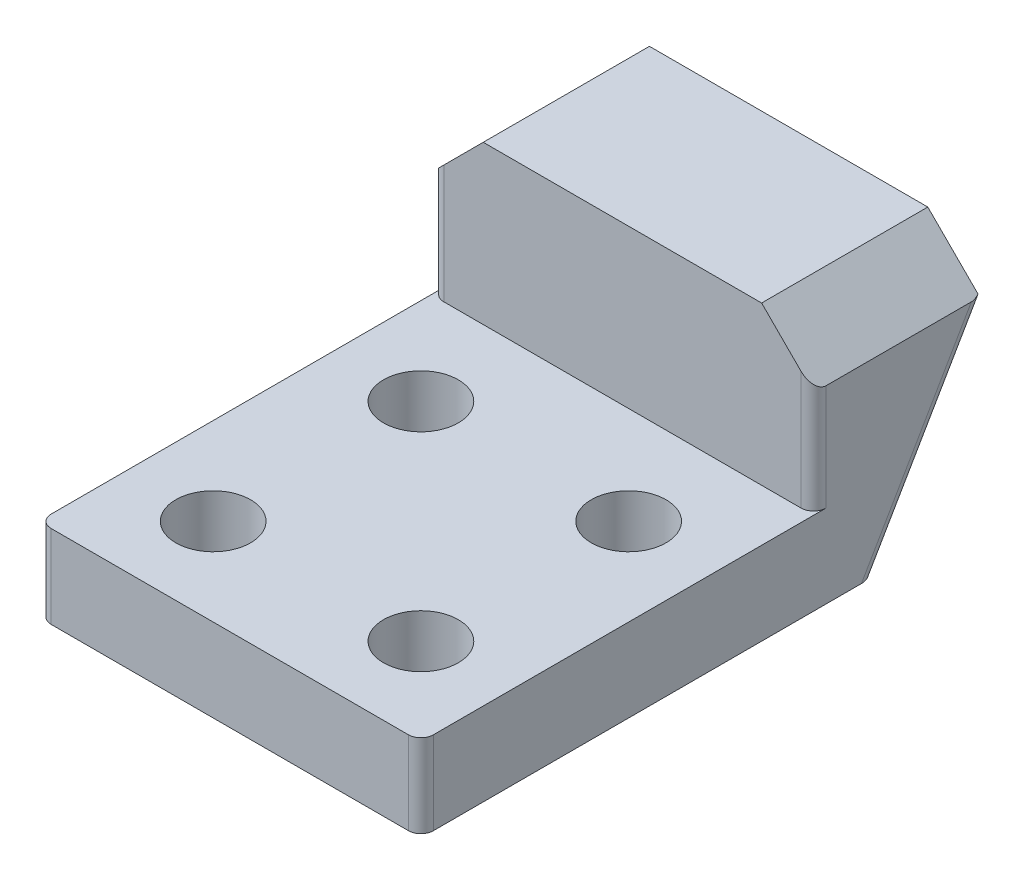
SolidWorks part; units mm, degrees
ref_plane "Front Plane" through (0, 0, 0) normal (0, 0, 1) x (1, 0, 0)
ref_plane "Top Plane" through (0, 0, 0) normal (0, 1, 0) x (1, 0, 0)
ref_plane "Right Plane" through (0, 0, 0) normal (1, 0, 0) x (0, 0, -1)
sketch "Sketch1" plane through (0, 0, 0) normal (0, 1, 0) x (1, 0, 0)
  line L1 (0, 0) -> (18.4, 0)
  line L2 (0, 0) -> (0, 21.9)
  line L3 (0, 21.9) -> (18.4, 21.9)
  line L4 (18.4, 0) -> (18.4, 21.9)
  dimension "D1" = 18.4
  dimension "D2" = 21.9
extrude "Boss-Extrude1" add sketch "Sketch1" along normal blind 4
sketch "Sketch2" plane through (0, 4, 0) normal (0, 1, 0) x (1, 0, 0)
  line L0 (9.2, 0) -> (9.2, 21.9) construction
  line L1 (0, 0) -> (18.4, 0) construction
  line L2 (18.4, 21.9) -> (0, 21.9) construction
  line L4 (4.2, 4.2) -> (4.2, 14.2) construction
  point P0 (4.2, 4.2)
  point P15 (4.2, 14.2)
  point P18 (3.1567, 13.0582)
  point P21 (14.2, 14.2)
  point P22 (14.2, 4.2)
  point P23 (0, 0)
  dimension "D1" = 5
  dimension "D2" = 10
  dimension "D3" = 4.2
hole_wizard "M3 Clearance Hole1" positions "Sketch2" profile "Sketch3" hole size "M3" standard "ANSI Metric" end condition through all
sketch "Sketch3" plane through (4.2, 4, -4.2) normal (1, 0, 0) x (0, 0, 1)
  line L0 (0, 0) -> (0, 4)
  line L1 (0, 4) -> (1.8, 4)
  line L2 (1.8, 4) -> (1.8, 0)
  line L5 (1.8, 0) -> (0, 0)
  line L11 (0, -6.35) -> (0, 107.95) construction
  dimension "Thru Hole Dia." = 3.6
  dimension "Thru Hole Depth" = 4
sketch "Sketch4" plane through (0, 0, -21.9) normal (0, 0, -1) x (-1, 0, 0)
  line L0 (-18.4, 4) -> (-18.4, 0) construction
  line L1 (0, 0) -> (-18.4, 0)
  line L2 (0, 0) -> (0, 8.6)
  line L3 (0, 8.6) -> (-18.4, 8.6)
  line L4 (-18.4, 0) -> (-18.4, 8.6)
  line L5 (-18.4, 4) -> (0, 4) construction
  line L6 (-18.4, 4) -> (0, 4) construction
  dimension "D1" = 4.6
extrude "Boss-Extrude2" add sketch "Sketch4" against normal blind 3
sketch "Sketch5" plane through (0, 8.6, 0) normal (0, 1, 0) x (1, 0, 0)
  line L0 (18.4, 18.9) -> (18.4, 21.9) construction
  line L1 (0, 18.9) -> (18.4, 18.9)
  line L2 (0, 18.9) -> (0, 26.9)
  line L3 (0, 26.9) -> (18.4, 26.9)
  line L4 (18.4, 18.9) -> (18.4, 26.9)
  line L5 (0, 21.9) -> (18.4, 21.9) construction
  line L6 (0, 21.9) -> (18.4, 21.9) construction
  dimension "D1" = 5
extrude "Boss-Extrude3" add sketch "Sketch5" along normal blind 3
chamfer "Chamfer1" distance 2.5 angle 45 2 edges at (18.4, 11.6, -22.9) (0, 11.6, -22.9)
chamfer "Chamfer2" distance 5 distance2 8.6 1 edges at (9.2, 8.6, -21.9) first distance on face at (9.2, 8.6, -24.4)
fillet "Fillet1" radius 0.6 6 edges at (0, 4.3, -24.4) (18.4, 4.3, -24.4) (0, 6.55, -18.9) (18.4, 6.55, -18.9) (0, 2, 0) (18.4, 2, 0)
